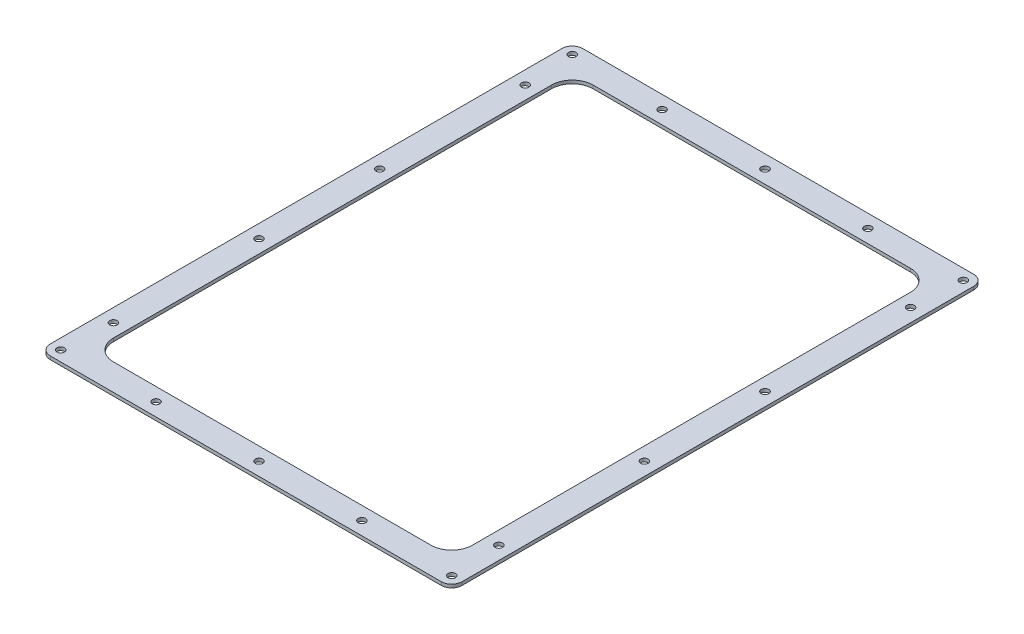
SolidWorks part; units mm, degrees
ref_plane "Front Plane" through (0, 0, 0) normal (0, 0, 1) x (1, 0, 0)
ref_plane "Top Plane" through (0, 0, 0) normal (0, 1, 0) x (1, 0, 0)
ref_plane "Right Plane" through (0, 0, 0) normal (1, 0, 0) x (0, 0, -1)
sketch "Sketch1" plane through (0, 0, 0) normal (0, 1, 0) x (1, 0, 0)
  line L1 (-99, -128) -> (99, -128)
  line L2 (-99, -128) -> (-99, 128)
  line L3 (-99, 128) -> (99, 128)
  line L4 (99, -128) -> (99, 128)
  line L5 (-99, -128) -> (99, 128) construction
  line L6 (-99, 128) -> (99, -128) construction
  line L7 (-86.3, -115.3) -> (86.3, -115.3)
  line L8 (-86.3, -115.3) -> (-86.3, 115.3)
  line L9 (-86.3, 115.3) -> (86.3, 115.3)
  line L10 (86.3, -115.3) -> (86.3, 115.3)
  line L11 (-86.3, -115.3) -> (86.3, 115.3) construction
  line L12 (-86.3, 115.3) -> (86.3, -115.3) construction
  point P0 (0, 0)
  point P6 (0, 0)
  dimension "D1" = 198
  dimension "D2" = 256
  dimension "D3" = 12.7
  dimension "D4" = 12.7
extrude "MainBody" add sketch "Sketch1" along normal blind 1.5875
hole_wizard "M3 Clearance Hole1" positions "Sketch2" profile "Sketch3" hole size "M3" standard "ANSI Metric" end condition up to next
sketch "Sketch2" plane through (0, 1.5875, 0) normal (0, 1, 0) x (1, 0, 0)
  line L0 (0, 0) -> (-99, 0) construction
  line L1 (-99, 128) -> (-99, -128) construction
  line L3 (0, 0) -> (0, 128) construction
  line L4 (99, 128) -> (-99, 128) construction
  line L6 (0, 64) -> (-99, 64) construction
  line L10 (-86.3, 99) -> (-99, 99) construction
  line L11 (-86.3, 115.3) -> (-86.3, -115.3) construction
  line L16 (-99, 108.5349) -> (0, 108.5349) construction
  line L18 (-49.5, 115.3) -> (-49.5, 128) construction
  line L19 (86.3, 115.3) -> (-86.3, 115.3) construction
  point P0 (-92.65, 99)
  point P23 (-92.65, 29)
  point P24 (-92.65, -29)
  point P25 (-92.65, -99)
  point P31 (92.65, -99)
  point P32 (92.65, -29)
  point P33 (92.65, 29)
  point P34 (92.65, 99)
  point P36 (0, 121.65)
  point P53 (-92.65, 99)
  point P66 (-49.5, 108.5349)
  point P78 (-49.5, 121.65)
  point P81 (-49.5, 121.65)
  point P93 (49.5, -121.65)
  point P94 (0, -121.65)
  point P95 (-49.5, -121.65)
  point P98 (49.5, 121.65)
  dimension "D1" = 35
sketch "Sketch3" plane through (-92.65, 1.5875, -99) normal (1, 0, 0) x (0, 0, 1)
  line L0 (0, 0) -> (0, 1.5875)
  line L1 (0, 1.5875) -> (1.8, 1.5875)
  line L2 (1.8, 1.5875) -> (1.8, 0)
  line L5 (1.8, 0) -> (0, 0)
  line L11 (0, -6.35) -> (0, 107.95) construction
  dimension "Thru Hole Dia." = 3.6
  dimension "Thru Hole Depth" = 1.5875
fillet "InsideFillet" radius 10 4 edges at (-86.3, 0.7937, 115.3) (86.3, 0.7937, 115.3) (86.3, 0.7937, -115.3) (-86.3, 0.7937, -115.3)
fillet "Fillet2" radius 5 4 edges at (-99, 0.7937, 128) (99, 0.7937, 128) (99, 0.7937, -128) (-99, 0.7937, -128)
hole_wizard "M3 Clearance Hole2" positions "Sketch4" profile "Sketch5" hole size "M3" standard "ANSI Metric" end condition through all
sketch "Sketch4" plane through (0, 1.5875, 0) normal (0, 1, 0) x (1, 0, 0)
  point P0 (-94, 123)
  point P3 (94, 123)
  point P6 (94, -122.975)
  point P9 (-94, -123)
sketch "Sketch5" plane through (-94, 1.5875, -123) normal (1, 0, 0) x (0, 0, 1)
  line L0 (0, 0) -> (0, 1.5875)
  line L1 (0, 1.5875) -> (1.8, 1.5875)
  line L2 (1.8, 1.5875) -> (1.8, 0)
  line L5 (1.8, 0) -> (0, 0)
  line L11 (0, -6.35) -> (0, 107.95) construction
  dimension "Thru Hole Dia." = 3.6
  dimension "Thru Hole Depth" = 1.5875
equation "\"Width\"= 225mm"
equation "\"D1@Sketch1\"=\"InternalWidth\" - \"InnerEdgeTol\" * 2"
equation "\"Length\"= 283mm"
equation "\"WallThickness\"= 12.5mm"
equation "\"UpperWaterJacketThickness\"= 28mm"
equation "\"SpacerHeight\"= 80.2mm"
equation "\"SpacerCornerWidth\"= 10mm"
equation "\"SpacerCornerHeight\"= 60.16mm"
equation "\"SpacerPegDiameter\"= 10mm"
equation "\"SpacerPegHeight\"= 10mm"
equation "\"TubingShort\"= 110mm"
equation "\"TubingLong\"= 175mm"
equation "\"PlateLength\"= 252mm"
equation "\"PlateWidth\"= 190mm"
equation "\"PlateHoleDiameter\"= 5.9mm"
equation "\"PlateHoleBottom\"= 2mm"
equation "\"PlateHoleSide\"= 1.55mm"
equation "\"PlateHoleSpacing\"= 3.1mm"
equation "\"PlateThickness\"= 1.55mm"
equation "\"ReservoirBottom\"= 12.5mm"
equation "\"ReservoirSupportWidth\"= 12mm"
equation "\"ReservoirSupportHeight\"= 15.1mm"
equation "\"ReservoirSupportPlacementHeight\"= 50mm"
equation "\"ReservoirHoleDiameter\"= 12.7mm"
equation "\"ReservoirHoleRight\"= 25mm"
equation "\"ReservoirHoleTop\"= \"ReservoirSupportPlacementHeight\""
equation "\"ReservoirHeight\"= 90mm"
equation "\"ReservoirPortBottom\"= 4mm"
equation "\"ReservoirPortTop\"= 10mm"
equation "\"ReservoirPortWidth\"= 101mm"
equation "\"CustomSpacerWallThickness\"= 0.375in"
equation "\"CustomSpacerHeight\"= 5in"
equation "\"CustomSpacerRodHoleHeight\"= .75in"
equation "\"CustomSpacerRodHoleDiameter\"= .3125in"
equation "\"ScrewBlockSide\"= 12mm"
equation "\"ScrewBlockUpperHeight\"= 16mm"
equation "\"ScrewBlockLowerHeight\"= 16mm"
equation "\"InternalLength\"= 258mm"
equation "\"InternalWidth\"= 200mm"
equation "\"CustomSpacerPegHeight\"= 1in"
equation "\"CustomSpacerScrewBore\"=3.2mm"
equation "\"CustomSpacerScrewDepth\"=10mm"
equation "\"D2@Sketch1\"=\"InternalLength\" - \"InnerEdgeTol\" * 2"
equation "\"D4@Sketch1\"=0.5in"
equation "\"InnerEdgeTol\"= 1mm"
